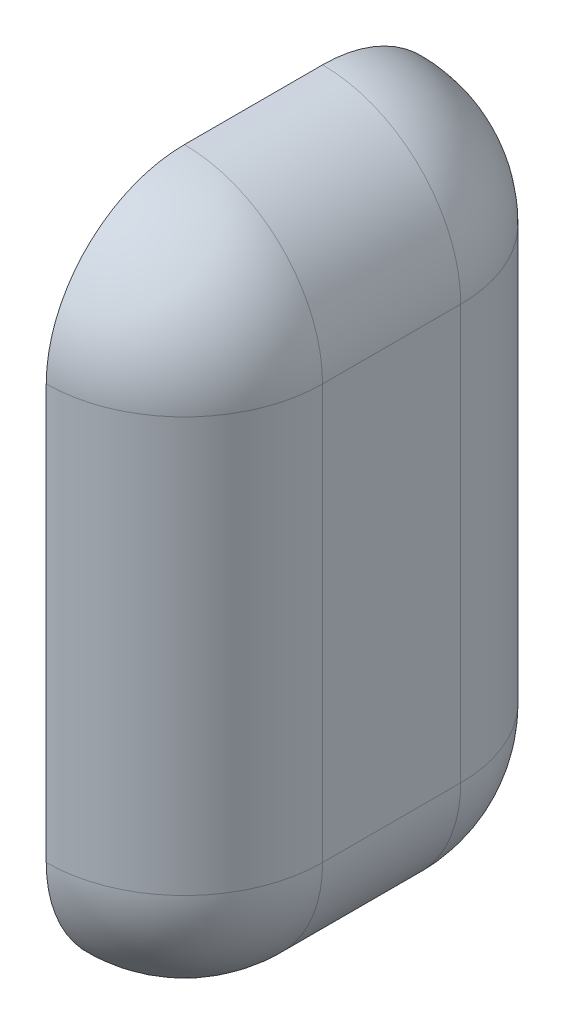
SolidWorks part; units mm, degrees
material "Rubber"
ref_plane "Front" through (0, 0, 0) normal (0, 0, 1) x (1, 0, 0)
ref_plane "Top" through (0, 0, 0) normal (0, 1, 0) x (1, 0, 0)
ref_plane "Right" through (0, 0, 0) normal (1, 0, 0) x (0, 0, -1)
sketch "Sketch1" plane through (0, 0, 0) normal (1, 0, 0) x (0, 0, -1)
  line L9 (-0.4445, 0.9525) -> (0.4445, 0.9525)
  line L10 (0.4445, 0.9525) -> (0.4445, -0.9525)
  line L13 (0.4445, -0.9525) -> (0.254, -1.2065)
  line L14 (0.254, -1.2065) -> (-0.254, -1.2065)
  line L15 (-0.254, -1.2065) -> (-0.4445, -0.9525)
  line L16 (-0.4445, -0.9525) -> (-0.4445, 0.9525)
  line L17 (0.4445, 0.9525) -> (-0.4445, -0.9525) construction
  line L18 (-0.4445, 0.9525) -> (0.4445, -0.9525) construction
  point P4 (0, 0)
  dimension "D1" = 0.508
  dimension "D2" = 2.159
  dimension "D3" = 0.889
  dimension "D4" = 1.905
extrude "Boss-Extrude1" add sketch "Sketch1" along normal blind 0.635
sketch "Sketch2" plane through (0.635, 0, 0) normal (1, 0, 0) x (0, 0, -1)
  line L1 (-1.905, -3.175) -> (1.905, -3.175)
  line L2 (-1.905, -3.175) -> (-1.905, 3.175)
  line L3 (-1.905, 3.175) -> (1.905, 3.175)
  line L4 (1.905, -3.175) -> (1.905, 3.175)
  line L5 (-1.905, -3.175) -> (1.905, 3.175) construction
  line L6 (-1.905, 3.175) -> (1.905, -3.175) construction
  point P0 (0, 0)
  dimension "D1" = 3.81
  dimension "D2" = 6.35
extrude "Boss-Extrude2" add sketch "Sketch2" along normal blind 1.27
fillet "Fillet4" radius 1.27 2 edges at (1.905, -3.175, 0) (1.905, 3.175, 0)
fillet "Fillet5" radius 1.27 6 edges at (1.533, 2.803, 1.905) (1.533, -2.803, 1.905) (1.533, -2.803, -1.905) (1.533, 2.803, -1.905) (1.905, 0, 1.905) (1.905, 0, -1.905)
